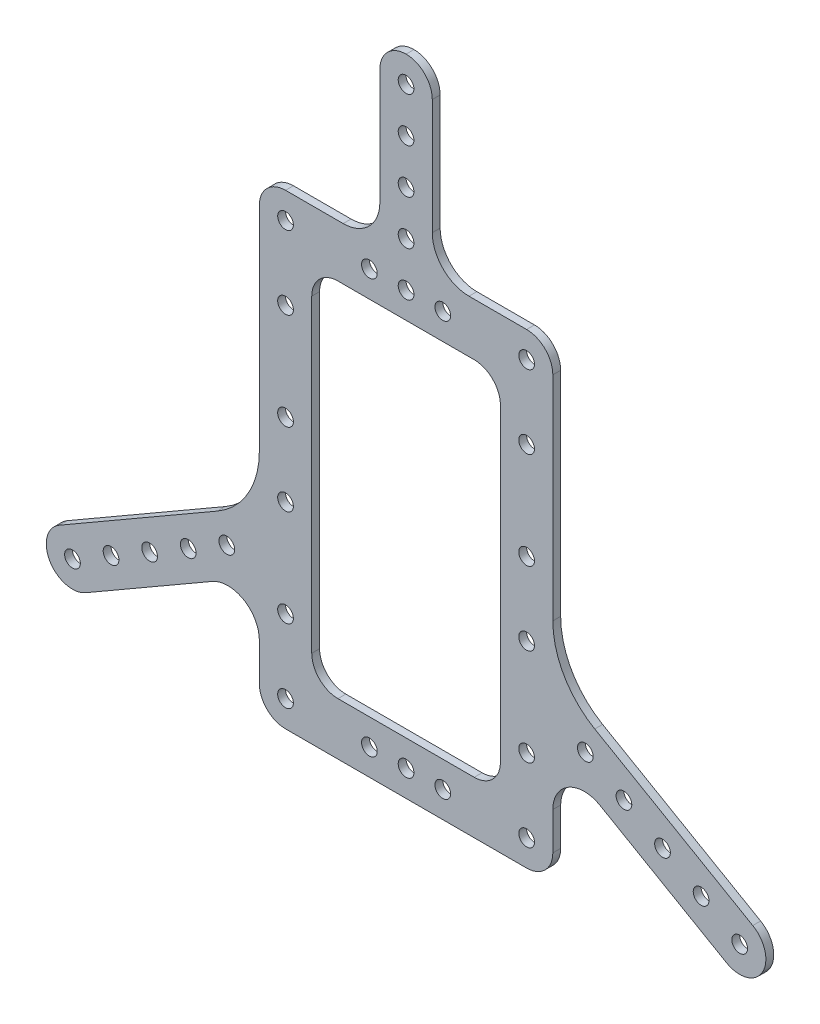
SolidWorks part; units mm, degrees
material "Carbon Fiber"
ref_plane "前视基准面" through (0, 0, 0) normal (0, 0, 1) x (1, 0, 0)
ref_plane "上视基准面" through (0, 0, 0) normal (0, 1, 0) x (1, 0, 0)
ref_plane "右视基准面" through (0, 0, 0) normal (1, 0, 0) x (0, 0, -1)
sketch "草图1" plane through (0, 0, 0) normal (0, 0, 1) x (1, 0, 0)
  line L6 (-23, 39.5) -> (23, 39.5) construction
  line L9 (-23, 39.5) -> (-23, -39.5) construction
  line L24 (-23, -39.5) -> (23, -39.5) construction
  line L25 (23, 39.5) -> (23, -39.5) construction
  line L26 (-23, 39.5) -> (23, -39.5) construction
  line L27 (-23, -39.5) -> (23, 39.5) construction
  line L28 (23, -39.5) -> (-23, -39.5) construction
  line L29 (23, -39.5) -> (23, 25.5) construction
  line L30 (23, 25.5) -> (-23, 25.5) construction
  line L31 (-23, -39.5) -> (-23, 25.5) construction
  line L55 (0, 39.5) -> (0, 73.5) construction
  line L56 (0, 0) -> (-63.6529, -36.75) construction
  line L58 (18, 34.5) -> (-18, 34.5)
  line L59 (18, 34.5) -> (18, -34.5)
  line L60 (18, -34.5) -> (-18, -34.5)
  line L61 (-18, 34.5) -> (-18, -34.5)
  line L62 (18, 34.5) -> (-18, -34.5) construction
  line L63 (18, -34.5) -> (-18, 34.5) construction
  line L64 (-28, -25.5) -> (28, -25.5) construction
  line L65 (28, 44.5) -> (5, 44.5)
  line L66 (28, 44.5) -> (28, -10.3923)
  line L67 (28, -44.5) -> (-28, -44.5)
  line L68 (-28, 44.5) -> (-28, -10.3923)
  line L69 (28, 44.5) -> (-28, -44.5) construction
  line L70 (28, -44.5) -> (-28, 44.5) construction
  line L71 (0, 0) -> (63.6529, -36.75) construction
  line L72 (-5, 44.5) -> (-5, 78.5)
  line L73 (5, 44.5) -> (5, 78.5)
  line L74 (-28, -10.3923) -> (-70.483, -34.9199)
  line L75 (-28, -21.9393) -> (-65.483, -43.5801)
  line L76 (28, -10.3923) -> (70.483, -34.9199)
  line L77 (28, -21.9393) -> (65.483, -43.5801)
  line L78 (-70.483, -34.9199) -> (-65.483, -43.5801)
  line L79 (70.483, -34.9199) -> (65.483, -43.5801)
  line L80 (-5, 78.5) -> (5, 78.5)
  line L81 (-28, -21.9393) -> (-28, -44.5)
  line L82 (28, -21.9393) -> (28, -44.5)
  line L83 (-5, 44.5) -> (-28, 44.5)
  line L84 (-23, 0) -> (23, 0) construction
  circle A3 centre (23, -39.5) radius 1.5
  circle A4 centre (-23, -39.5) radius 1.5
  circle A5 centre (-23, 39.5) radius 1.5
  circle A6 centre (23, 39.5) radius 1.5
  circle A7 centre (-23, 25.5) radius 1.5
  circle A8 centre (23, 25.5) radius 1.5
  circle A9 centre (23, -25.5) radius 1.5
  circle A10 centre (-23, -25.5) radius 1.5
  circle A11 centre (0, 0) radius 73.5 construction
  circle A12 centre (0, 39.5) radius 1.5
  circle A13 centre (0, 73.5) radius 1.5
  circle A14 centre (-63.6529, -36.75) radius 1.5
  circle A15 centre (-34.208, -19.75) radius 1.5
  circle A16 centre (63.6529, -36.75) radius 1.5
  circle A17 centre (34.208, -19.75) radius 1.5
  circle A18 centre (0, -39.5) radius 1.5
  circle A19 centre (7, -39.5) radius 1.5
  circle A20 centre (-7, -39.5) radius 1.5
  circle A21 centre (7, 39.5) radius 1.5
  circle A22 centre (-7, 39.5) radius 1.5
  circle A23 centre (-23, 7) radius 1.5
  circle A24 centre (-23, -7) radius 1.5
  circle A25 centre (23, 7) radius 1.5
  circle A26 centre (23, -7) radius 1.5
  circle A27 centre (0, 65) radius 1.5
  circle A28 centre (0, 56.5) radius 1.5
  circle A29 centre (0, 48) radius 1.5
  circle A30 centre (56.2917, -32.5) radius 1.5
  circle A31 centre (48.9304, -28.25) radius 1.5
  circle A32 centre (41.5692, -24) radius 1.5
  circle A33 centre (-56.2917, -32.5) radius 1.5
  circle A34 centre (-48.9304, -28.25) radius 1.5
  circle A35 centre (-41.5692, -24) radius 1.5
  point P0 (0, 0)
  dimension "D4" = 3
  dimension "D5" = 5
  dimension "D7" = 34
  dimension "D6" = 5
  dimension "D11" = 14
  dimension "D12" = 120
  dimension "D19" = 3
  dimension "D25" = 7
  dimension "D29" = 7
  dimension "D1" = 46
  dimension "D2" = 79
  dimension "D3" = 14
  dimension "D8" = 120
  dimension "D9" = 5
  dimension "D10" = 5
  dimension "D13" = 5
  dimension "D14" = 5
  dimension "D15" = 5
  dimension "D16" = 5
  dimension "D17" = 5
  dimension "D18" = 5
  dimension "D20" = 34
  dimension "D21" = 34
  dimension "D22" = 5
  dimension "D23" = 5
  dimension "D24" = 5
  dimension "D26" = 7
  dimension "D27" = 7
  dimension "D28" = 7
  dimension "D30" = 7
  dimension "D31" = 7
  dimension "D32" = 7
  dimension "D33" = 4
extrude "凸台-拉伸1" add sketch "草图1" along normal blind 1.5
fillet "圆角1" radius 5 8 edges at (18, -34.5, 0.75) (-18, -34.5, 0.75) (28, -44.5, 0.75) (-28, -44.5, 0.75) (18, 34.5, 0.75) (-18, 34.5, 0.75) (28, 44.5, 0.75) (-28, 44.5, 0.75)
fillet "圆角2" radius 6 2 edges at (28, -21.9393, 0.75) (-28, -21.9393, 0.75)
fillet "圆角3" radius 16 2 edges at (-28, -10.3923, 0.75) (28, -10.3923, 0.75)
fillet "圆角4" radius 7 2 edges at (-5, 44.5, 0.75) (5, 44.5, 0.75)
fillet "圆角5" radius 5 6 edges at (5, 78.5, 0.75) (-5, 78.5, 0.75) (65.483, -43.5801, 0.75) (70.483, -34.9199, 0.75) (-65.483, -43.5801, 0.75) (-70.483, -34.9199, 0.75)
